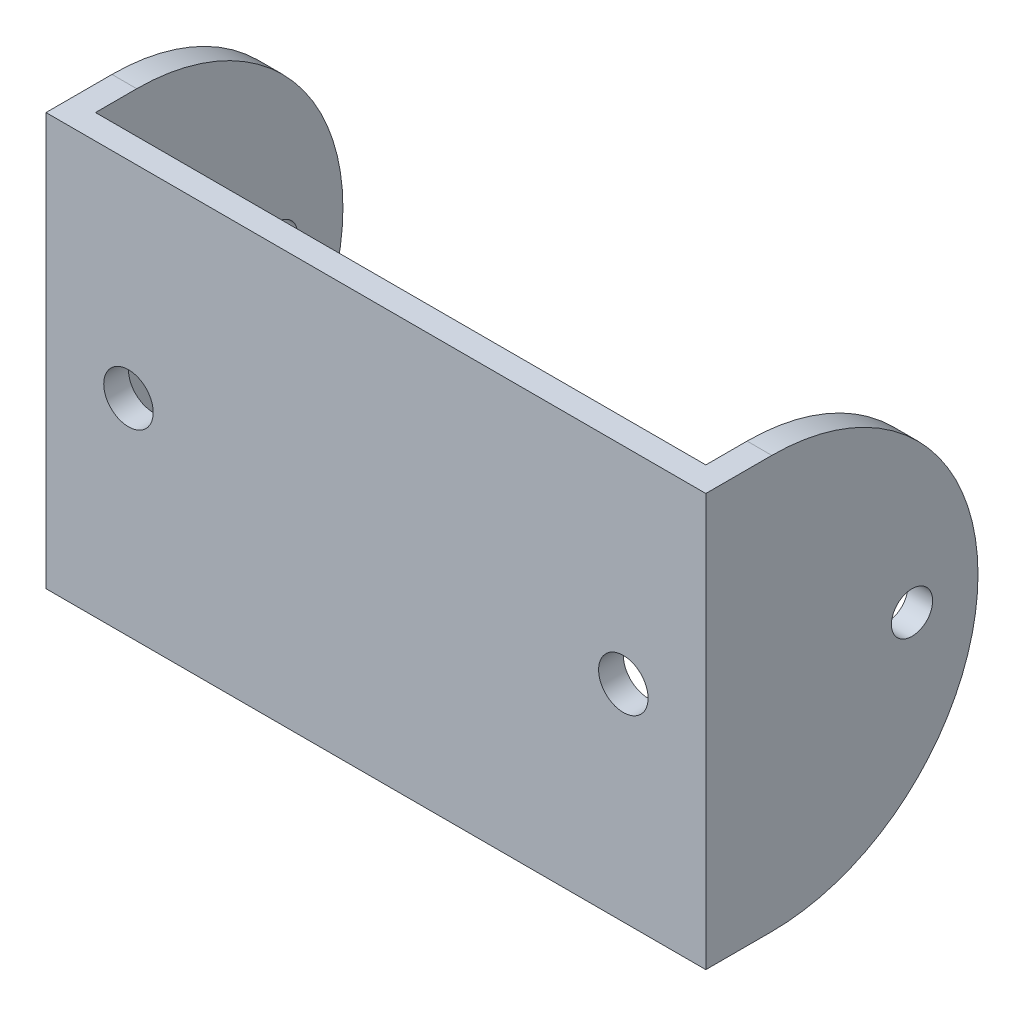
SolidWorks part; units mm, degrees
ref_plane "Front Plane" through (0, 0, 0) normal (0, 0, 1) x (1, 0, 0)
ref_plane "Top Plane" through (0, 0, 0) normal (0, 1, 0) x (1, 0, 0)
ref_plane "Right Plane" through (0, 0, 0) normal (1, 0, 0) x (0, 0, -1)
sketch "Sketch1" plane through (0, 0, 0) normal (0, 0, 1) x (1, 0, 0)
  line L1 (-40, -25) -> (40, -25)
  line L2 (-40, -25) -> (-40, 25)
  line L3 (-40, 25) -> (40, 25)
  line L4 (40, -25) -> (40, 25)
  line L5 (-40, -25) -> (40, 25) construction
  line L6 (-40, 25) -> (40, -25) construction
  point P0 (0, 0)
  dimension "D1" = 80
  dimension "D2" = 50
extrude "Boss-Extrude1" add sketch "Sketch1" along normal blind 3
sketch "Sketch2" plane through (0, 0, 0) normal (0, 0, -1) x (-1, 0, 0)
  line L0 (-40, 0) -> (40, 0) construction
  line L1 (-40, -25) -> (-40, 25) construction
  line L2 (40, 25) -> (40, -25) construction
  line L3 (-40, 25) -> (40, 25) construction
  line L4 (0, 25) -> (0, -25) construction
  line L5 (40, -25) -> (-40, -25) construction
  circle A0 centre (-30, 0) radius 3
  circle A1 centre (30, 0) radius 3
  dimension "D1" = 60
  dimension "D2" = 6
extrude "Cut-Extrude1" cut sketch "Sketch2" against normal up to next
sketch "Sketch3" plane through (0, 0, 0) normal (0, 0, -1) x (-1, 0, 0)
  line L0 (40, -25) -> (-40, -25) construction
  line L1 (-40, 25) -> (-37, 25)
  line L2 (-40, 25) -> (-40, -25)
  line L3 (-40, -25) -> (-37, -25)
  line L4 (-37, 25) -> (-37, -25)
  line L5 (0, 25) -> (0, -25) construction
  line L6 (-40, 25) -> (40, 25) construction
  line L7 (40, -25) -> (37, -25)
  line L8 (37, 25) -> (37, -25)
  line L9 (40, 25) -> (37, 25)
  line L10 (40, 25) -> (40, -25)
  dimension "D1" = 3
extrude "Boss-Extrude2" add sketch "Sketch3" along normal blind 30
fillet "Fillet1" 2 edges at (38.5, 25, -30) (38.5, -25, -30) type full round first side face at (0, 25, -14.25) second side face at (0, -25, -14.25) middle face at (38.5, 0, -30)
fillet "Fillet2" 2 edges at (-38.5, 25, -30) (-38.5, -25, -30) type full round first side face at (0, 25, -8) second side face at (0, -25, -8) middle face at (-38.5, 0, -30)
sketch "Sketch4" plane through (40, 0, 0) normal (1, 0, 0) x (0, 0, -1)
  line L0 (-3, -25) -> (-3, 25) construction
  line L2 (-3, 25) -> (5, 25) construction
  circle A1 centre (22, 0) radius 2.5
  dimension "D1" = 5
  dimension "D2" = 25
  dimension "D3" = 25
extrude "Cut-Extrude2" cut sketch "Sketch4" against normal blind 200
